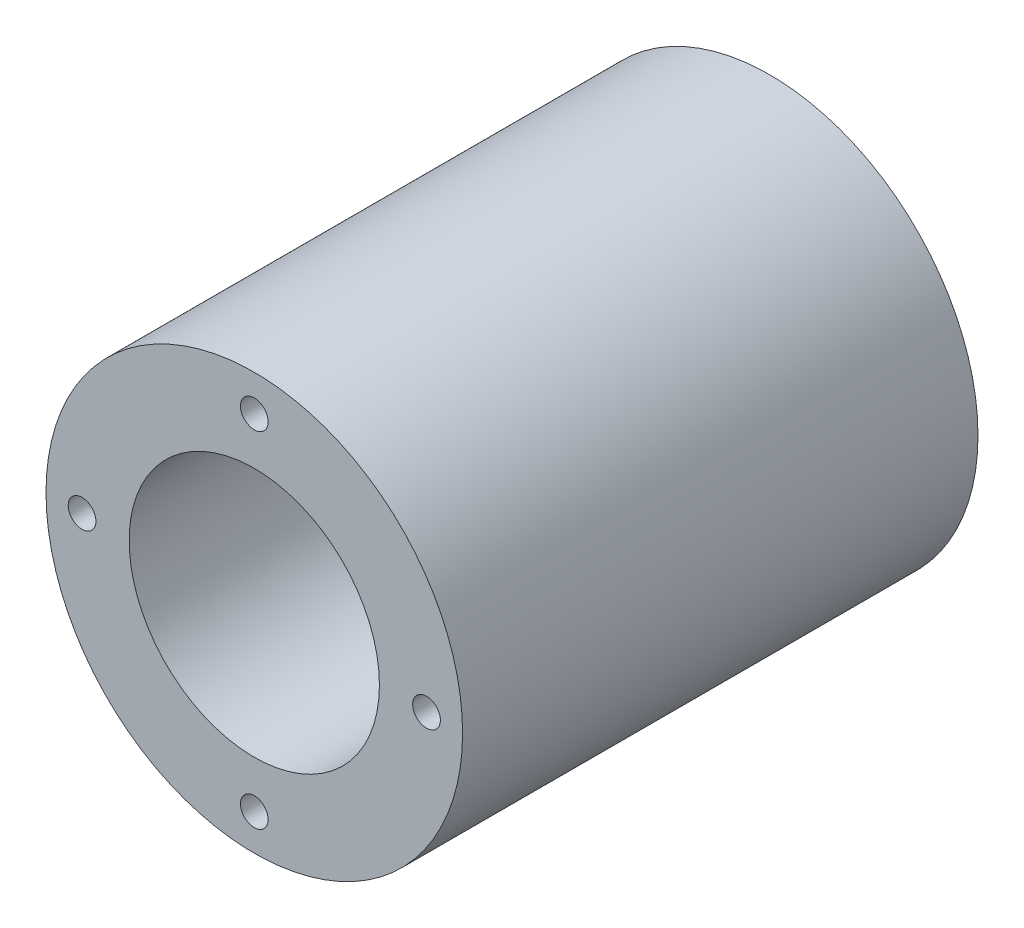
SolidWorks part; units mm, degrees
material "6061-T6 (SS)"
ref_plane "Front Plane" through (0, 0, 0) normal (0, 0, 1) x (1, 0, 0)
ref_plane "Top Plane" through (0, 0, 0) normal (0, 1, 0) x (1, 0, 0)
ref_plane "Right Plane" through (0, 0, 0) normal (1, 0, 0) x (0, 0, -1)
sketch "Sketch Spindle Skeleton" plane through (0, 0, 0) normal (1, 0, 0) x (0, 0, -1)
  line L0 (-95.847, -9.525) -> (-140.95, -9.525)
  line L5 (-1000, 0) -> (49000, 0)
  line L6 (0, -9.525) -> (0, 9.525)
  line L13 (0, 9.525) -> (-45.847, 9.525)
  line L26 (-45.847, 9.525) -> (-45.847, 14)
  line L27 (-45.847, 14) -> (-95.847, 14)
  line L32 (-95.847, 14) -> (-95.847, 9.525)
  line L34 (-160, 7) -> (-160, -7)
  line L36 (-95.847, -9.525) -> (-95.847, -14)
  line L37 (-95.847, -14) -> (-45.847, -14)
  line L38 (-45.847, -14) -> (-45.847, -9.525)
  line L39 (0, -9.525) -> (-45.847, -9.525)
  line L40 (-25.305, 37.6491) -> (-16.305, 37.6491)
  line L41 (-111.341, 22.6187) -> (-95.847, 22.6187)
  line L42 (-111.341, 22.6187) -> (-111.341, -22.6187)
  line L43 (-111.341, -22.6187) -> (-95.847, -22.6187)
  line L44 (-95.847, 22.6187) -> (-95.847, -22.6187)
  line L45 (-111.341, 22.6187) -> (-95.847, -22.6187) construction
  line L46 (-111.341, -22.6187) -> (-95.847, 22.6187) construction
  line L47 (-30.353, 22.6187) -> (-45.847, 22.6187)
  line L48 (-30.353, 22.6187) -> (-30.353, -22.6187)
  line L49 (-30.353, -22.6187) -> (-45.847, -22.6187)
  line L50 (-45.847, 22.6187) -> (-45.847, -22.6187)
  line L51 (-30.353, 22.6187) -> (-45.847, -22.6187) construction
  line L52 (-30.353, -22.6187) -> (-45.847, 22.6187) construction
  line L59 (-16.305, 37.6491) -> (-16.305, -37.6491)
  line L60 (-16.305, -37.6491) -> (-25.305, -37.6491)
  line L61 (-25.305, -22.6187) -> (-27.305, -22.6187)
  line L62 (-27.305, -22.6187) -> (-27.305, -12.5)
  line L63 (-27.305, -12.5) -> (-25.305, -12.5)
  line L64 (-25.305, -12.5) -> (-25.305, 12.5)
  line L65 (-25.305, 12.5) -> (-27.305, 12.5)
  line L66 (-27.305, 12.5) -> (-27.305, 22.6187)
  line L67 (-27.305, 22.6187) -> (-25.305, 22.6187)
  line L68 (-25.305, 22.6187) -> (-25.305, 37.6491)
  line L69 (-25.305, -22.6187) -> (-25.305, -37.6491)
  line L71 (-119.469, 37.6491) -> (-26.305, 37.6491)
  line L72 (-119.469, 37.6491) -> (-119.469, -37.6491)
  line L73 (-119.469, -37.6491) -> (-26.305, -37.6491)
  line L74 (-26.305, 37.6491) -> (-26.305, -37.6491)
  line L75 (-119.469, 37.6491) -> (-26.305, -37.6491) construction
  line L76 (-119.469, -37.6491) -> (-26.305, 37.6491) construction
  line L77 (-140.95, -9.525) -> (-140.95, -7)
  line L78 (-140.95, -7) -> (-160, -7)
  line L79 (-95.847, 9.525) -> (-140.95, 9.525)
  line L80 (-140.95, 7) -> (-160, 7)
  line L81 (-140.95, 9.525) -> (-140.95, 7)
  line L82 (-118.3985, 9.525) -> (-118.3985, -9.525) construction
  line L83 (-22.9235, 9.525) -> (-22.9235, -9.525) construction
  line L96 (-119.469, 37.6492) -> (-134.709, 37.6492)
  line L98 (-119.469, -37.6491) -> (-134.709, -37.6491)
  line L99 (-134.709, 37.6492) -> (-134.709, -37.6491)
  line L110 (-119.469, 37.6492) -> (-119.469, -37.6491)
  point P3 (0, 0)
  point P18 (-103.594, 0)
  point P24 (-38.1, 0)
  point P29 (-72.887, 0)
  point P48 (-16.305, 31.1339)
  point P58 (0, 0)
  point P59 (0, 0)
  point P70 (-134.709, 31.1339)
sketch "Sketch1" plane through (0, 0, 0) normal (1, 0, 0) x (0, 0, -1)
  line L0 (-26.305, 37.6491) -> (-26.305, -37.6491) construction
  line L1 (-119.469, -37.6491) -> (-26.305, -37.6491) construction
  line L2 (-119.469, 37.6491) -> (-119.469, -37.6491) construction
  line L3 (-119.469, 37.6491) -> (-26.305, 37.6491) construction
  line L4 (-26.305, 37.6491) -> (-26.305, -37.6491)
  line L5 (-119.469, -37.6491) -> (-26.305, -37.6491)
  line L6 (-119.469, 37.6491) -> (-119.469, -37.6491)
  line L7 (-119.469, 37.6491) -> (-26.305, 37.6491)
  line L9 (-30.353, 22.6187) -> (-45.847, 22.6187) construction
  line L10 (-119.469, 22.6187) -> (-26.305, 22.6187)
  line L15 (-119.469, 0) -> (-26.305, 0) construction
revolve "Revolve1" add sketch "Sketch1" angle 360 about L15 region at (0, 30.1339, 72.887)
sketch "Back Hole Top Location" plane through (0, 0, 26.305) normal (0, 0, -1) x (-1, 0, 0)
  point P9 (0, 31.1339)
hole_wizard "M6x1.0 Tapped Hole3" positions "Sketch8" profile "Sketch9" tap size "M6x1.0" standard "ANSI Metric"
sketch "Sketch8" plane through (0, 0, 26.305) normal (0, 0, -1) x (-1, 0, 0)
  point P0 (0, 31.1339)
sketch "Sketch9" plane through (0, 31.1339, 26.305) normal (1, 0, 0) x (0, 1, 0)
  line L0 (0, 0) -> (0, 16.5022)
  line L1 (0, 16.5022) -> (2.5, 15)
  line L2 (2.5, 15) -> (2.5, 0)
  line L5 (2.5, 0) -> (0, 0)
  line L10 (0, 16.5022) -> (-2.5, 15) construction
  line L11 (0, -6.35) -> (0, 107.95) construction
  dimension "Tap Drill Dia." = 5
  dimension "Tap Drill Depth" = 15
  dimension "Drill Angle" = 118
pattern_circular "BackFacePattern" count 6 over 360 about axis through (0, 0, 1000) along (0, 0, -1) of "M6x1.0 Tapped Hole3"
ref_plane "Midplane" through (0, 0, 72.887) normal (0, 0, -1) x (-1, 0, 0)
sketch "Front Hole Top Location" plane through (0, 0, 119.469) normal (0, 0, 1) x (1, 0, 0)
  point P0 (0, 31.1339)
hole_wizard "M6x1.0 Tapped Hole2" positions "Sketch5" profile "Sketch6" tap size "M6x1.0" standard "ANSI Metric"
sketch "Sketch5" plane through (0, 0, 119.469) normal (0, 0, 1) x (1, 0, 0)
  point P0 (0, 31.1339)
sketch "Sketch6" plane through (0, 31.1339, 119.469) normal (1, 0, 0) x (0, -1, 0)
  line L0 (0, 0) -> (0, 16.5022)
  line L1 (0, 16.5022) -> (2.5, 15)
  line L2 (2.5, 15) -> (2.5, 0)
  line L5 (2.5, 0) -> (0, 0)
  line L10 (0, 16.5022) -> (-2.5, 15) construction
  line L11 (0, -6.35) -> (0, 107.95) construction
  dimension "Tap Drill Dia." = 5
  dimension "Tap Drill Depth" = 15
  dimension "Drill Angle" = 118
pattern_circular "FrontFacePattern" count 4 over 360 about axis through (0, 0, 1000) along (0, 0, -1) of "M6x1.0 Tapped Hole2"
sketch "Sketch7" plane through (0, 0, 26.305) normal (0, 0, -1) x (-1, 0, 0)
  circle A0 centre (0, 0) radius 26.9875
  circle A1 centre (0, 0) radius 24.6062
  dimension "D1" = 53.975
  dimension "D2" = 49.2125
extrude "Cut-Extrude1" cut sketch "Sketch7" against normal blind 0.5
